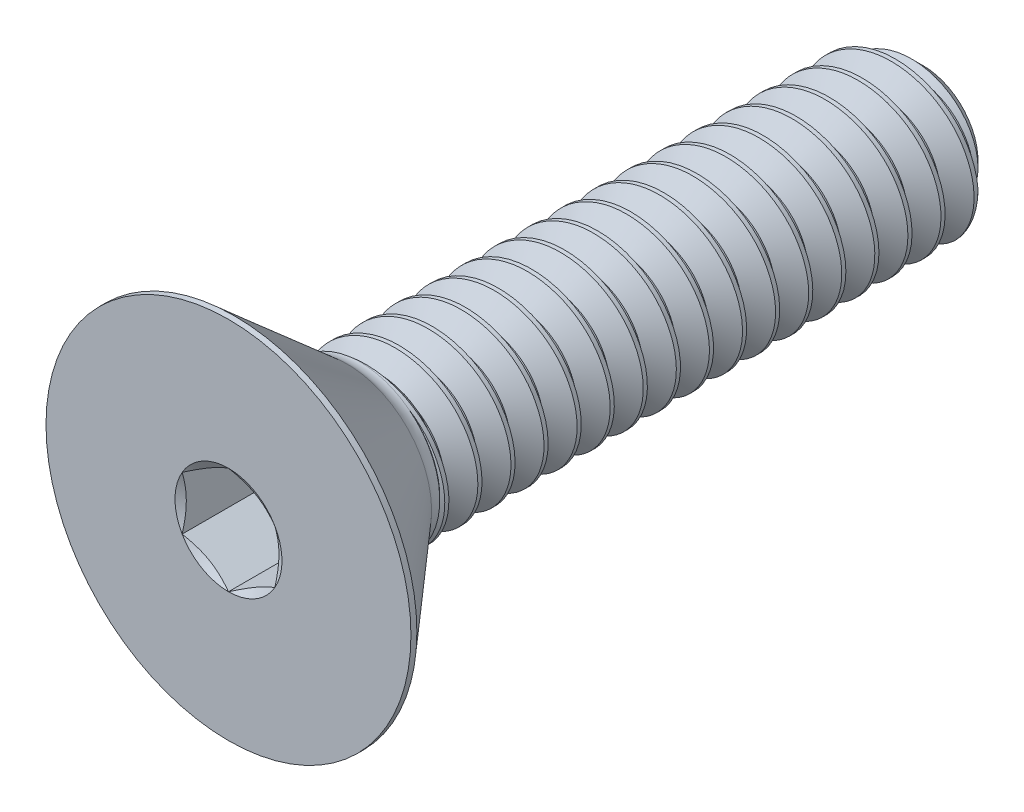
SolidWorks part; units mm, degrees
material "Alloy Steel"
ref_plane "Front" through (0, 0, 0) normal (0, 0, 1) x (1, 0, 0)
ref_plane "Top" through (0, 0, 0) normal (0, 1, 0) x (1, 0, 0)
ref_plane "Right" through (0, 0, 0) normal (1, 0, 0) x (0, 0, -1)
sketch "Sketch1" plane through (0, 0, 0) normal (1, 0, 0) x (0, 0, -1)
  line L0 (0, 2.5019) -> (0.0813, 2.5019) construction
  line L1 (0.0813, 2.5019) -> (1.6256, 1.1594) construction
  line L2 (0, 1.0922) -> (9.525, 1.0922)
  line L3 (9.525, 1.0922) -> (9.525, 0)
  line L4 (9.525, 0) -> (0, 0)
  line L5 (0, 0) -> (0, 2.5019) construction
  line L6 (0, 2.5019) -> (0, -2.5019) construction
  line L7 (9.525, 1.0922) -> (9.525, -1.0922) construction
  line L8 (0, -2.5019) -> (0.0813, -2.5019) construction
  line L9 (0.0813, -2.5019) -> (1.6256, -1.1594) construction
  line L11 (0, 1.0922) -> (0, 0)
  line L12 (1.8054, 1.0922) -> (1.8054, 0) construction
  line L13 (-15.875, 0) -> (-15.875, 1.0922) construction
  arc A1 (1.6256, 1.1594) -> (1.8054, 1.0922) centre (1.8054, 1.3663) ccw construction
  dimension "D1" = 0.0813
  dimension "Min Thread" = 25.4
revolve "Revolve1" add sketch "Sketch1" angle 360 mid plane about L4
sketch "Sketch3" plane through (0, 0, -9.525) normal (0, 0, -1) x (-1, 0, 0)
  circle A0 centre (0, 0) radius 1.0922
curve "Helix/Spiral1" pitch 0.4536 height 9.525 radius 1.0922 centre (0, 0, -9.525) axis (0, 0, 1) start towards (0, 1, 0)
sketch "Sketch2" plane through (0, 0, 0) normal (1, 0, 0) x (0, 0, -1)
  line L0 (9.525, 1.0922) -> (9.9219, 1.0922)
  line L1 (9.9219, 1.0922) -> (9.7518, 0.7976)
  line L2 (9.7518, 0.7976) -> (9.6951, 0.7976)
  line L3 (9.6951, 0.7976) -> (9.525, 1.0922)
  line L4 (9.61, 0.9449) -> (9.8368, 0.9449) construction
  dimension "D1" = 60
  dimension "D2" = 0.0567
  dimension "D3" = 0.2268
ref_plane "Plane2" through (0, 0, 15.875) normal (0, 0, 1) x (1, 0, 0)
chamfer "Chamfer1" distance 0.3402 angle 45 1 edges at (0, 1.0922, -9.525)
sweep "Cut-Sweep1" cut profiles "Sketch2" path "Helix/Spiral1" align with end faces yes
sketch "Sketch7" plane through (0, 0, 0) normal (1, 0, 0) x (0, 0, -1)
  line L0 (0, 2.5019) -> (0.0813, 2.5019) construction
  line L1 (0.0813, 2.5019) -> (1.6256, 1.1594) construction
  line L2 (0, 2.5019) -> (0.0813, 2.5019)
  line L3 (0.0813, 2.5019) -> (1.6256, 1.1594)
  line L4 (1.8054, 1.0922) -> (1.8054, 0) construction
  line L5 (1.8054, 1.0922) -> (1.8054, 0)
  line L7 (0, 0) -> (0, 2.5019) construction
  line L8 (0, 0) -> (0, 2.5019)
  line L9 (0, 0) -> (1.8054, 0)
  line L10 (5.7417, 0) -> (-5.7417, 0) construction
  arc A0 (1.6256, 1.1594) -> (1.8054, 1.0922) centre (1.8054, 1.3663) ccw construction
  arc A1 (1.6256, 1.1594) -> (1.8054, 1.0922) centre (1.8054, 1.3663) ccw
revolve "Revolve2" add sketch "Sketch7" angle 360 mid plane about L9
ref_plane "Plane1" through (0, 0, -1.8054) normal (0, 0, 1) x (1, 0, 0)
sketch "Sketch8" plane through (0, 0, -1.8054) normal (0, 0, 1) x (1, 0, 0)
  circle A0 centre (0, 0) radius 1.0922
extrude "Boss-Extrude1" add sketch "Sketch8" against normal through all draft 46
sketch "Sketch5" plane through (0, 0, 0) normal (0, 0, 1) x (1, 0, 0)
  line L0 (0, 0) -> (-0.7332, 0) construction
  line L1 (0, 0) -> (-2.7496, 1.5875) construction
  line L2 (0, 0) -> (-2.7496, -1.5875) construction
  line L6 (0, 0.7332) -> (0, 0.6047) construction
  line L7 (0, 0.6047) -> (0, 0.4763) construction
  line L9 (0, 0.7332) -> (-0.635, 0.3666)
  line L10 (-0.635, 0.3666) -> (-0.635, -0.3666)
  line L11 (-0.635, -0.3666) -> (0, -0.7332)
  line L12 (0, -0.7332) -> (0.635, -0.3666)
  line L13 (0.635, -0.3666) -> (0.635, 0.3666)
  line L14 (0.635, 0.3666) -> (0, 0.7332)
  circle A0 centre (0, 0) radius 0.7332 construction
  circle A1 centre (0, 0) radius 0.6047 construction
  circle A2 centre (0, 0) radius 0.4763 construction
  circle A3 centre (0, 0) radius 0.635 construction
  dimension "D3" = 0.9525
  dimension "D4" = 30
  dimension "D5" = 30
  dimension "Hex" = 1.27
extrude "Cut-Extrude2" cut sketch "Sketch5" against normal blind 1.1379
sketch "Sketch6" plane through (0, 0, 0) normal (0, 0, 1) x (1, 0, 0)
  circle A0 centre (0, 0) radius 0.7332
extrude "Cut-Extrude3" cut sketch "Sketch6" against normal blind 1.1379 draft 60
sketch "Sketch9" [suppressed] plane through (0, 0, -3.6076) normal (0, 0, 1) x (1, 0, 0)
  circle A1 centre (0, 0) radius 2.413
  circle A2 centre (0, 0) radius 2.413
  point P0 (0, 2.413)
  dimension "D1" = 0
extrude "Boss-Extrude2" [suppressed] add sketch "Sketch9" against normal up to surface (15.4424 mm away) up to plane "Plane2"
sketch "Sketch10" plane through (0, 0, 0) normal (1, 0, 0) x (0, 0, -1)
  line L0 (9.525, 1.0922) -> (9.525, -1.0922) construction
  point P0 (8.8446, -1.0922)
  dimension "D1" = 0.6804
equation "\"D3@Helix/Spiral1\" = \"Lg@Sketch1\""
equation "\"D2@Sketch2\" = \"D4@Helix/Spiral1\" * .125"
equation "\"D3@Sketch2\" = \"D4@Helix/Spiral1\" * .5"
equation "\"D1@Chamfer1\" = \"D4@Helix/Spiral1\" * .75"
equation "\"D1@Cut-Extrude2\" = \"Head Ht@Sketch1\" * .7"
equation "\"D1@Sketch1\" = \"Head Ht@Sketch1\" * .05"
equation "\"D1@Sketch10\" = \"D4@Helix/Spiral1\" * 1.5"
equation "\"D1@Cut-Extrude3\" = \"D1@Cut-Extrude2\""
equation "\"D3@Sketch5\" = \"Hex@Sketch5\" * .75"
